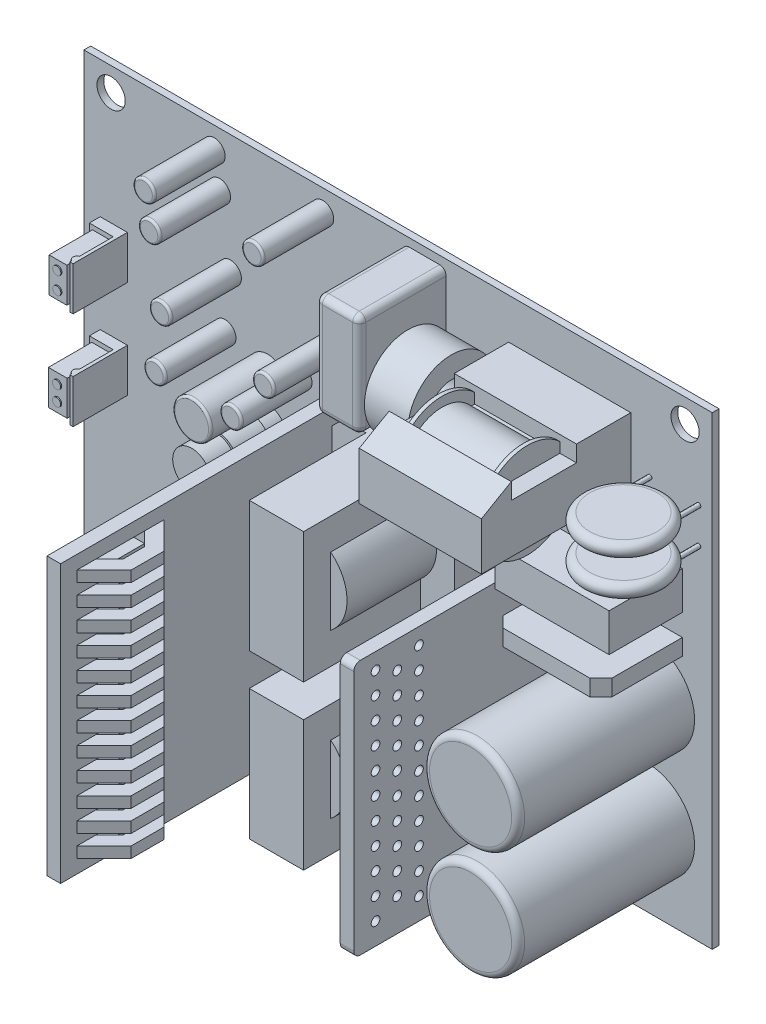
SolidWorks part; units mm, degrees
material "PW50:34:C1:0:1:2:Re:16:"
ref_plane "Front" through (0, 0, 0) normal (0, 0, 1) x (1, 0, 0)
ref_plane "Top" through (0, 0, 0) normal (0, 1, 0) x (1, 0, 0)
ref_plane "Side" through (0, 0, 0) normal (1, 0, 0) x (0, 0, -1)
sketch "Sketch1" plane through (0, 0, 0) normal (0, 0, 1) x (1, 0, 0)
  line L0 (-73.4695, 40.132) -> (-73.4695, -68.58)
  line L2 (-73.4695, -68.58) -> (73.4695, -68.58)
  line L4 (-73.4695, 40.132) -> (73.4695, 40.132)
  line L5 (73.4695, 40.132) -> (73.4695, -68.58)
  circle A3 centre (67.1195, 34.6075) radius 3.302
  circle A5 centre (-67.1195, 34.6075) radius 3.302
extrude "Base-Extrude" add sketch "Sketch1" along normal blind 1.5875
sketch "Sketch3" plane through (0, 0, 1.5875) normal (0, 0, 1) x (1, 0, 0)
  line L0 (73.4695, 40.132) -> (73.4695, -68.58) construction
  line L1 (-73.4695, -68.58) -> (73.4695, -68.58) construction
  circle A0 centre (58.2295, -49.53) radius 11.1125
  circle A1 centre (58.2295, -24.13) radius 11.1125
  dimension "D1" = 22.225
  dimension "D4" = 25.4
  dimension "D2" = 15.24
  dimension "D3" = 19.05
extrude "Boss-Extrude1" add sketch "Sketch3" along normal blind 41.275
fillet "Fillet1" radius 1.524 2 edges at (69.342, -24.13, 42.8625) (69.342, -49.53, 42.8625)
sketch "Sketch4" plane through (0, 0, 1.5875) normal (0, 0, 1) x (1, 0, 0)
  line L0 (66.4845, -8.89) -> (41.0845, -8.89)
  line L1 (66.4845, -8.89) -> (66.4845, -12.7)
  line L2 (41.0845, -12.7) -> (66.4845, -12.7)
  line L3 (41.0845, -12.7) -> (41.0845, -8.89)
  line L4 (-73.4695, -68.58) -> (73.4695, -68.58) construction
  line L5 (73.4695, 40.132) -> (73.4695, -68.58) construction
  dimension "D1" = 25.4
  dimension "D2" = 3.81
  dimension "D3" = 59.69
  dimension "D4" = 6.985
extrude "Boss-Extrude2" add sketch "Sketch4" along normal blind 19.05
chamfer "Chamfer1" distance 2.54 angle 45 2 edges at (66.4845, -10.795, 20.6375) (41.0845, -10.795, 20.6375)
sketch "Sketch5" plane through (0, 0, 1.5875) normal (0, 0, 1) x (1, 0, 0)
  line L0 (39.8145, 5.08) -> (66.4845, 5.08)
  line L1 (39.8145, 5.08) -> (39.8145, -3.81)
  line L2 (66.4845, -3.81) -> (39.8145, -3.81)
  line L3 (66.4845, -3.81) -> (66.4845, 5.08)
  line L4 (-73.4695, -68.58) -> (73.4695, -68.58) construction
  line L5 (73.4695, 40.132) -> (73.4695, -68.58) construction
  dimension "D1" = 26.67
  dimension "D2" = 8.89
  dimension "D3" = 73.66
  dimension "D4" = 6.985
extrude "Boss-Extrude3" add sketch "Sketch5" along normal blind 17.145
ref_plane "Plane4" through (0, 19.812, 0) normal (0, 1, 0) x (-1, 0, 0)
sketch "Sketch6" plane through (0, 19.812, 0) normal (0, 1, 0) x (-1, 0, 0)
  line L0 (-64.5795, -2.54) -> (-64.5795, 29.21) construction
  line L2 (-70.2945, 1.5875) -> (-70.2945, 6.7362)
  line L3 (-58.8645, 1.5875) -> (-58.8645, 6.7362)
  line L6 (73.4695, 1.5875) -> (-73.4695, 1.5875) construction
  arc A0 (-58.2116, 8.7074) -> (-70.9474, 8.7074) centre (-64.5795, 13.4459) ccw
  arc A1 (-58.2116, 8.7074) -> (-58.8645, 6.7362) centre (-55.5625, 6.7362) ccw
  arc A2 (-70.9474, 8.7074) -> (-70.2945, 6.7362) centre (-73.5965, 6.7362) cw
  point P13 (-58.8645, 7.9375)
  dimension "D4" = 3.302
  dimension "D5" = 5.715
  dimension "D6" = 8.89
  dimension "D3" = 7.9375
  dimension "D1" = 5.1487
  dimension "D2" = 11.8584
sketch "Sketch7" plane through (0, 0, 1.5875) normal (0, 0, 1) x (1, 0, 0)
  circle A0 centre (70.2945, 19.812) radius 0.508
  dimension "D1" = 1.016
sweep "Boss-Sweep1" add profiles "Sketch7" path "Sketch6"
ref_plane "Plane5" through (0, 0, 13.4493) normal (0, 0, 1) x (1, 0, 0)
sketch "Sketch8" plane through (0, 0, 13.4493) normal (0, 0, 1) x (1, 0, 0)
  line L0 (73.4695, 40.132) -> (73.4695, -68.58) construction
  line L1 (-73.4695, 40.132) -> (73.4695, 40.132) construction
  line L2 (72.4493, 21.463) -> (64.5795, 21.463)
  line L3 (64.5795, 19.812) -> (64.5795, 13.7195) construction
  line L4 (64.5795, 21.463) -> (64.5795, 18.161)
  line L5 (72.4493, 18.161) -> (64.5795, 18.161)
  arc A0 (72.4493, 18.161) -> (72.4493, 21.463) centre (72.4493, 19.812) ccw
  dimension "D1" = 3.302
  dimension "D2" = 20.32
  dimension "D3" = 1.0202
  dimension "D4" = 8.89
revolve "Boss-Revolve1" add sketch "Sketch8" angle 360 about L3
pattern_linear "LPattern1" count 2 spacing 8.255 along (0, -1, 0) of "Boss-Revolve1", "Boss-Sweep1"
sketch "Sketch9" plane through (0, 0, 1.5875) normal (0, 0, 1) x (1, 0, 0)
  line L0 (25.8445, 30.607) -> (54.4195, 30.607)
  line L1 (25.8445, 30.607) -> (25.8445, 11.557)
  line L2 (54.4195, 11.557) -> (25.8445, 11.557)
  line L3 (54.4195, 11.557) -> (54.4195, 30.607)
  line L4 (-73.4695, 40.132) -> (73.4695, 40.132) construction
  line L5 (73.4695, 40.132) -> (73.4695, -68.58) construction
  dimension "D1" = 28.575
  dimension "D2" = 19.05
  dimension "D3" = 9.525
  dimension "D4" = 19.05
extrude "Boss-Extrude4" add sketch "Sketch9" along normal blind 34.925
sketch "Sketch10" plane through (54.4195, 0, 0) normal (1, 0, 0) x (0, 0, -1)
  line L0 (-29.5275, 30.607) -> (-42.1593, 23.314)
  line L1 (-14.2875, 40.132) -> (-14.2875, -68.58)
  line L2 (-14.2875, 40.132) -> (-14.2875, 26.797)
  line L3 (-29.5275, 40.132) -> (-29.5275, -68.58)
  line L4 (-29.5275, 30.607) -> (-29.5275, 26.797)
  line L5 (-36.5125, 15.367) -> (-1.5875, 15.367)
  line L6 (-42.1593, 15.367) -> (-14.2875, 15.367)
  line L7 (-36.5125, 26.797) -> (-1.5875, 26.797)
  line L8 (-29.5275, 26.797) -> (-14.2875, 26.797)
  line L9 (-36.5125, 30.607) -> (-1.5875, 30.607) construction
  line L10 (-14.2875, 7.4511) -> (-47.8412, 7.4511)
  line L11 (-47.8412, 7.4511) -> (-47.8412, 40.132)
  line L12 (-47.8412, 40.132) -> (-14.2875, 40.132)
  line L13 (-14.2875, 15.367) -> (-14.2875, 7.4511)
  line L14 (-42.1593, 23.314) -> (-42.1593, 15.367)
  dimension "D5" = 27.8718
  dimension "D6" = 33.5537
  dimension "D7" = 32.6809
  dimension "D8" = 30
  dimension "D1" = 12.7
  dimension "D2" = 27.94
  dimension "D3" = 3.81
  dimension "D4" = 3.81
extrude "Cut-Extrude1" cut sketch "Sketch10" against normal through all
ref_plane "Plane6" through (54.4195, 0, 0) normal (-1, 0, 0) x (0, 0, 1)
ref_plane "Plane7" through (40.132, 0, 0) normal (-1, 0, 0) x (0, 0, 1)
sketch "Sketch11" plane through (40.132, 0, 0) normal (-1, 0, 0) x (0, 0, 1)
  line L0 (14.2875, 15.367) -> (14.2875, 26.797) construction
  line L1 (14.2875, 21.082) -> (29.5275, 21.082) construction
  line L3 (29.5275, 30.607) -> (29.5275, 26.797) construction
  circle A0 centre (21.9075, 21.082) radius 8.89
  dimension "D1" = 17.78
extrude "Boss-Extrude5" add sketch "Sketch11" along normal mid plane 19.05
sketch "Sketch12" plane through (49.657, 0, 0) normal (1, 0, 0) x (0, 0, -1)
  circle A0 centre (-21.9075, 21.082) radius 11.1125
  dimension "D1" = 22.225
extrude "Boss-Extrude6" add sketch "Sketch12" along normal blind 0.889
sketch "Sketch13" plane through (30.607, 0, 0) normal (-1, 0, 0) x (0, 0, 1)
  circle A0 centre (21.9075, 21.082) radius 11.1125
  arc A1 (29.5275, 29.1705) -> (14.2875, 29.1705) centre (21.9075, 21.082) ccw construction
extrude "Boss-Extrude7" add sketch "Sketch13" along normal blind 0.889
ref_plane "Plane8" through (17.272, 0, 0) normal (-1, 0, 0) x (0, 0, 1)
sketch "Sketch14" plane through (17.272, 0, 0) normal (-1, 0, 0) x (0, 0, 1)
  line L0 (21.9075, 21.082) -> (15.647, 21.082) construction
  line L1 (1.5875, 40.132) -> (1.5875, -68.58) construction
  circle A0 centre (11.4935, 21.082) radius 10.16
  circle A1 centre (11.4935, 21.082) radius 5.08
  dimension "D1" = 20.32
  dimension "D2" = 10.16
  dimension "D3" = 9.906
extrude "Boss-Extrude8" add sketch "Sketch14" along normal mid plane 10.16
sketch "Sketch15" plane through (0, 0, 1.5875) normal (0, 0, 1) x (1, 0, 0)
  line L0 (2.6035, 14.097) -> (9.7155, 14.097)
  line L1 (1.0795, 15.621) -> (1.0795, 36.703)
  line L2 (9.7155, 38.227) -> (2.6035, 38.227)
  line L3 (11.2395, 36.703) -> (11.2395, 15.621)
  line L4 (73.4695, 40.132) -> (73.4695, -68.58) construction
  line L5 (-73.4695, 40.132) -> (73.4695, 40.132) construction
  arc A0 (1.0795, 15.621) -> (2.6035, 14.097) centre (2.6035, 15.621) ccw
  arc A1 (11.2395, 15.621) -> (9.7155, 14.097) centre (9.7155, 15.621) cw
  arc A2 (11.2395, 36.703) -> (9.7155, 38.227) centre (9.7155, 36.703) ccw
  arc A3 (2.6035, 38.227) -> (1.0795, 36.703) centre (2.6035, 36.703) ccw
  dimension "D5" = 1.524
  dimension "D1" = 62.23
  dimension "D2" = 10.16
  dimension "D3" = 1.905
  dimension "D4" = 24.13
extrude "Boss-Extrude9" add sketch "Sketch15" along normal blind 20.32
fillet "Fillet2" radius 1.524 8 edges at (10.7931, 14.5434, 21.9075) (11.2395, 26.162, 21.9075) (1.0795, 26.162, 21.9075) (1.5259, 14.5434, 21.9075) (6.1595, 14.097, 21.9075) (10.7931, 37.7806, 21.9075) (6.1595, 38.227, 21.9075) (1.5259, 37.7806, 21.9075)
sketch "Sketch16" plane through (0, 0, 1.5875) normal (0, 0, 1) x (1, 0, 0)
  line L0 (33.4645, -5.715) -> (36.6395, -5.715)
  line L1 (33.4645, -5.715) -> (33.4645, -65.405)
  line L2 (36.6395, -65.405) -> (33.4645, -65.405)
  line L3 (36.6395, -65.405) -> (36.6395, -5.715)
  line L4 (73.4695, 40.132) -> (73.4695, -68.58) construction
  line L5 (-73.4695, -68.58) -> (73.4695, -68.58) construction
  dimension "D1" = 36.83
  dimension "D2" = 3.175
  dimension "D3" = 3.175
  dimension "D4" = 59.69
extrude "Boss-Extrude10" add sketch "Sketch16" along normal blind 46.99
fillet "Fillet3" radius 1.524 2 edges at (35.052, -65.405, 48.5775) (35.052, -5.715, 48.5775)
sketch "Sketch17" plane through (36.6395, 0, 0) normal (1, 0, 0) x (0, 0, -1)
  line L0 (-48.5775, -63.881) -> (-48.5775, -7.239) construction
  line L1 (-47.0535, -65.405) -> (-1.5875, -65.405) construction
  circle A0 centre (-43.4975, -60.325) radius 1.016
  circle A2 centre (-33.3375, -60.325) radius 1.016
  dimension "D1" = 2.032
  dimension "D2" = 5.08
  dimension "D3" = 5.08
  dimension "D4" = 10.16
extrude "Cut-Extrude2" cut sketch "Sketch17" against normal through all
pattern_linear "LPattern2" count 11 spacing 5.08 along (0, 1, 0) of "Cut-Extrude2"
sketch "Sketch18" plane through (36.6395, 0, 0) normal (1, 0, 0) x (0, 0, -1)
  circle A0 centre (-38.4175, -57.785) radius 1.016
  circle A1 centre (-43.4975, -60.325) radius 1.016 construction
  circle A2 centre (-43.4975, -55.245) radius 1.016 construction
  dimension "D1" = 5.08
  dimension "D2" = 2.54
extrude "Cut-Extrude3" cut sketch "Sketch18" against normal through all
pattern_linear "LPattern3" count 10 spacing 5.08 along (0, 1, 0) of "Cut-Extrude3"
sketch "Sketch19" plane through (0, 0, 1.5875) normal (0, 0, 1) x (1, 0, 0)
  line L0 (-3.3655, -33.02) -> (20.1295, -33.02)
  line L1 (-5.9055, -35.56) -> (-5.9055, -60.96)
  line L2 (20.1295, -63.5) -> (-3.3655, -63.5)
  line L3 (22.6695, -60.96) -> (22.6695, -35.56)
  line L4 (73.4695, 40.132) -> (73.4695, -68.58) construction
  line L5 (-73.4695, -68.58) -> (73.4695, -68.58) construction
  line L6 (-3.3655, -33.02) -> (-5.9055, -35.56)
  line L9 (-5.9055, -60.96) -> (-3.3655, -63.5)
  line L11 (20.1295, -63.5) -> (22.6695, -60.96)
  line L13 (22.6695, -35.56) -> (20.1295, -33.02)
  dimension "D1" = 135
  dimension "D2" = 45
  dimension "D3" = 135
  dimension "D4" = 135
  dimension "D5" = 28.575
  dimension "D6" = 30.48
  dimension "D7" = 2.54
  dimension "D8" = 50.8
  dimension "D9" = 5.08
extrude "Boss-Extrude11" add sketch "Sketch19" along normal blind 36.83
sketch "Sketch20" plane through (0, 0, 38.4175) normal (0, 0, 1) x (1, 0, 0)
  line L0 (22.6695, -48.26) -> (-5.9055, -48.26) construction
  line L3 (22.6695, -60.96) -> (22.6695, -35.56) construction
  line L4 (-5.9055, -35.56) -> (-5.9055, -60.96) construction
  line L5 (8.382, -48.26) -> (8.382, -24.765) construction
  line L6 (33.4645, -24.765) -> (36.6395, -24.765) construction
  line L7 (2.032, -29.21) -> (2.032, -40.3289)
  line L9 (14.732, -29.21) -> (14.732, -40.3289)
  line L10 (2.032, -29.21) -> (-4.9437, -29.21)
  line L11 (2.032, -56.1911) -> (2.032, -67.31)
  line L12 (14.732, -56.1911) -> (14.732, -67.31)
  line L13 (14.732, -67.31) -> (21.7077, -67.31)
  line L18 (-4.9437, -29.21) -> (-9.7155, -33.9818)
  line L19 (-9.7155, -33.9818) -> (-9.7155, -62.5382)
  line L20 (-9.7155, -62.5382) -> (-4.9437, -67.31)
  line L21 (-4.9437, -67.31) -> (21.7077, -67.31)
  line L22 (21.7077, -67.31) -> (26.4795, -62.5382)
  line L23 (26.4795, -62.5382) -> (26.4795, -33.9818)
  line L24 (26.4795, -33.9818) -> (21.7077, -29.21)
  line L25 (21.7077, -29.21) -> (-4.9437, -29.21)
  line L26 (-4.9437, -29.21) -> (-9.7155, -33.9818)
  line L27 (-9.7155, -33.9818) -> (-9.7155, -62.5382)
  line L28 (-9.7155, -62.5382) -> (-4.9437, -67.31)
  line L29 (-4.9437, -67.31) -> (2.032, -67.31)
  line L30 (21.7077, -67.31) -> (26.4795, -62.5382)
  line L31 (26.4795, -62.5382) -> (26.4795, -33.9818)
  line L32 (26.4795, -33.9818) -> (21.7077, -29.21)
  line L33 (21.7077, -29.21) -> (14.732, -29.21)
  arc A0 (2.032, -40.3289) -> (2.032, -56.1911) centre (8.382, -48.26) ccw
  arc A1 (14.732, -56.1911) -> (14.732, -40.3289) centre (8.382, -48.26) ccw
  dimension "D2" = 20.32
  dimension "D1" = 12.7
  dimension "D3" = 3.81
extrude "Cut-Extrude4" cut sketch "Sketch20" against normal offset from surface (27.305 mm away) 9.525
sketch "Sketch21" plane through (0, 0, 38.4175) normal (0, 0, 1) x (1, 0, 0)
  line L0 (2.032, -33.02) -> (2.032, -40.3289) construction
  line L1 (2.032, -37.3547) -> (2.032, -59.1653)
  line L2 (14.732, -33.02) -> (14.732, -40.3289) construction
  line L3 (14.732, -37.3547) -> (14.732, -59.1653)
  line L4 (-0.3493, -37.3547) -> (2.032, -37.3547)
  line L5 (-0.3493, -59.1653) -> (2.032, -59.1653)
  line L6 (14.732, -37.3547) -> (17.1132, -37.3547)
  line L7 (14.732, -59.1653) -> (17.1132, -59.1653)
  arc A1 (17.1132, -59.1653) -> (17.1132, -37.3547) centre (8.382, -48.26) ccw
  arc A2 (17.1132, -59.1653) -> (17.1132, -37.3547) centre (8.382, -48.26) ccw
  arc A3 (-0.3493, -37.3547) -> (-0.3493, -59.1653) centre (8.382, -48.26) ccw
  arc A4 (-0.3493, -37.3547) -> (-0.3493, -59.1653) centre (8.382, -48.26) ccw
  dimension "D1" = 3.81
  dimension "D2" = 3.81
extrude "Cut-Extrude5" cut sketch "Sketch21" against normal blind 6.35
pattern_linear "LPattern4" count 2 spacing 38.1 along (0, 1, 0) of "Cut-Extrude5", "Cut-Extrude4", "Boss-Extrude11"
sketch "Sketch22" plane through (0, 0, 1.5875) normal (0, 0, 1) x (1, 0, 0)
  line L0 (-16.0655, -0.635) -> (-12.8905, -0.635)
  line L1 (-16.0655, -0.635) -> (-16.0655, -65.405)
  line L2 (-12.8905, -65.405) -> (-16.0655, -65.405)
  line L3 (-12.8905, -65.405) -> (-12.8905, -0.635)
  line L4 (-73.4695, -68.58) -> (73.4695, -68.58) construction
  line L5 (73.4695, 40.132) -> (73.4695, -68.58) construction
  dimension "D1" = 3.175
  dimension "D2" = 3.175
  dimension "D3" = 64.77
  dimension "D4" = 86.36
extrude "Boss-Extrude12" add sketch "Sketch22" along normal blind 66.04
sketch "Sketch23" plane through (0, -0.635, 0) normal (0, 1, 0) x (-1, 0, 0)
  line L0 (12.8905, 63.8175) -> (6.5405, 57.4675)
  line L1 (12.8905, 67.6275) -> (12.8905, 1.5875) construction
  line L2 (6.5405, 57.4675) -> (6.5405, 49.8475)
  line L3 (6.5405, 49.8475) -> (12.8905, 43.4975)
  line L4 (12.8905, 47.9876) -> (9.7155, 51.1626)
  line L5 (9.7155, 51.1626) -> (9.7155, 56.1524)
  line L6 (9.7155, 56.1524) -> (12.8905, 59.3274)
  line L7 (12.8905, 59.3274) -> (12.8905, 63.8175)
  line L8 (12.8905, 47.9876) -> (12.8905, 43.4975)
  line L9 (16.0655, 67.6275) -> (12.8905, 67.6275) construction
  dimension "D1" = 3.175
  dimension "D2" = 3.175
  dimension "D3" = 135
  dimension "D4" = 135
  dimension "D5" = 3.175
  dimension "D6" = 3.175
  dimension "D7" = 3.81
  dimension "D8" = 20.32
extrude "Boss-Extrude13" add sketch "Sketch23" against normal up to surface (64.77 mm away) up to face at (-14.478, -65.405, 34.6075)
sketch "Sketch24" plane through (0, 0, 67.6275) normal (0, 0, 1) x (1, 0, 0)
  line L2 (-16.1074, -32.385) -> (-48.09, -32.385) construction
  line L4 (-12.8905, -19.05) -> (-12.8905, -16.51)
  line L5 (-12.8905, -24.13) -> (-12.8905, -21.59)
  line L6 (-12.8905, -8.89) -> (-6.2865, -8.89)
  line L8 (-12.8905, -29.21) -> (-12.8905, -26.67)
  line L9 (-6.2865, -69.85) -> (-6.2865, -62.23)
  line L10 (-12.8905, -69.85) -> (-12.8905, -62.23)
  line L11 (-12.8905, -34.29) -> (-12.8905, -31.75)
  line L12 (-12.8905, -6.35) -> (-6.2865, -6.35)
  line L13 (-12.8905, -11.43) -> (-6.2865, -11.43)
  line L14 (-12.8905, -13.97) -> (-6.2865, -13.97)
  line L15 (-12.8905, -16.51) -> (-6.2865, -16.51)
  line L16 (-12.8905, -19.05) -> (-6.2865, -19.05)
  line L17 (-6.2865, -8.89) -> (-6.2865, -6.35)
  line L18 (-12.8905, -8.89) -> (-12.8905, -6.35)
  line L19 (-12.8905, -13.97) -> (-12.8905, -11.43)
  line L20 (-6.2865, -13.97) -> (-6.2865, -11.43)
  line L21 (-12.8905, -21.59) -> (-6.2865, -21.59)
  line L22 (-12.8905, -24.13) -> (-6.2865, -24.13)
  line L23 (-12.8905, -26.67) -> (-6.2865, -26.67)
  line L25 (-12.8905, -29.21) -> (-6.2865, -29.21)
  line L26 (-12.8905, -31.75) -> (-6.2865, -31.75)
  line L27 (-12.8905, -34.29) -> (-6.2865, -34.29)
  line L29 (-12.8905, -36.83) -> (-6.2865, -36.83)
  line L30 (-12.8905, -39.37) -> (-6.2865, -39.37)
  line L31 (-12.8905, -41.91) -> (-6.2865, -41.91)
  line L33 (-12.8905, -44.45) -> (-6.2865, -44.45)
  line L34 (-12.8905, -46.99) -> (-6.2865, -46.99)
  line L36 (-12.8905, -49.53) -> (-6.2865, -49.53)
  line L38 (-12.8905, -52.07) -> (-6.2865, -52.07)
  line L39 (-12.8905, -54.61) -> (-6.2865, -54.61)
  line L40 (-12.8905, -57.15) -> (-6.2865, -57.15)
  line L41 (-12.8905, -39.37) -> (-12.8905, -36.83)
  line L42 (-12.8905, -44.45) -> (-12.8905, -41.91)
  line L43 (-12.8905, -49.53) -> (-12.8905, -46.99)
  line L44 (-12.8905, -54.61) -> (-12.8905, -52.07)
  line L45 (-6.2865, -54.61) -> (-6.2865, -52.07)
  line L46 (-6.2865, -49.53) -> (-6.2865, -46.99)
  line L47 (-6.2865, -44.45) -> (-6.2865, -41.91)
  line L48 (-6.2865, -39.37) -> (-6.2865, -36.83)
  line L49 (-6.2865, -34.29) -> (-6.2865, -31.75)
  line L50 (-6.2865, -29.21) -> (-6.2865, -26.67)
  line L51 (-6.2865, -24.13) -> (-6.2865, -21.59)
  line L52 (-6.2865, -19.05) -> (-6.2865, -16.51)
  line L53 (-6.2865, -59.69) -> (-12.8905, -59.69)
  line L55 (-6.2865, -62.23) -> (-12.8905, -62.23)
  line L57 (-6.2865, -69.85) -> (-12.8905, -69.85)
  line L61 (-6.2865, -59.69) -> (-6.2865, -57.15)
  line L62 (-12.8905, -59.69) -> (-12.8905, -57.15)
  line L63 (-12.8905, -65.405) -> (-12.8905, -0.635) construction
  line L64 (-12.8905, -65.405) -> (-6.5405, -65.405) construction
  line L65 (-12.8905, -3.81) -> (-6.2865, -3.81)
  line L67 (-12.8905, -3.81) -> (-12.8905, -0.381)
  line L68 (-12.8905, -0.381) -> (-6.5405, -0.381)
  line L69 (-12.8905, -0.381) -> (-6.2865, -0.381)
  line L70 (-6.2865, -3.81) -> (-6.2865, -0.381)
  line L71 (-16.0655, -0.635) -> (-12.8905, -0.635) construction
  dimension "D2" = 2.54
  dimension "D4" = 2.54
  dimension "D5" = 2.54
  dimension "D6" = 2.54
  dimension "D7" = 2.54
  dimension "D8" = 2.54
  dimension "D9" = 2.54
  dimension "D10" = 2.54
  dimension "D11" = 2.54
  dimension "D12" = 2.54
  dimension "D13" = 2.54
  dimension "D14" = 2.54
  dimension "D15" = 2.54
  dimension "D16" = 2.54
  dimension "D17" = 2.54
  dimension "D18" = 2.54
  dimension "D1" = 2.54
  dimension "D3" = 2.54
  dimension "D19" = 2.54
  dimension "D20" = 2.54
  dimension "D21" = 63.5
  dimension "D22" = 3.175
  dimension "D23" = 2.54
  dimension "D24" = 2.54
  dimension "D25" = 6.604
  dimension "D26" = 2.54
  dimension "D27" = 0.254
  dimension "D28" = 3.175
extrude "Cut-Extrude6" cut sketch "Sketch24" against normal blind 25.4
sketch "Sketch25" plane through (-16.0655, 0, 0) normal (-1, 0, 0) x (0, 0, 1)
  line L0 (56.1524, -62.23) -> (51.1626, -62.23) construction
  line L1 (56.1524, -59.69) -> (51.1626, -59.69) construction
  line L2 (51.1626, -57.15) -> (56.1524, -57.15) construction
  line L3 (51.1626, -54.61) -> (56.1524, -54.61) construction
  line L4 (51.1626, -52.07) -> (56.1524, -52.07) construction
  line L5 (51.1626, -49.53) -> (56.1524, -49.53) construction
  line L6 (51.1626, -46.99) -> (56.1524, -46.99) construction
  line L7 (51.1626, -44.45) -> (56.1524, -44.45) construction
  line L8 (51.1626, -41.91) -> (56.1524, -41.91) construction
  line L9 (51.1626, -39.37) -> (56.1524, -39.37) construction
  line L10 (51.1626, -36.83) -> (56.1524, -36.83) construction
  line L11 (51.1626, -34.29) -> (56.1524, -34.29) construction
  line L12 (51.1626, -31.75) -> (56.1524, -31.75) construction
  line L13 (51.1626, -29.21) -> (56.1524, -29.21) construction
  line L14 (51.1626, -26.67) -> (56.1524, -26.67) construction
  line L15 (51.1626, -24.13) -> (56.1524, -24.13) construction
  line L16 (51.1626, -21.59) -> (56.1524, -21.59) construction
  line L17 (51.1626, -19.05) -> (56.1524, -19.05) construction
  line L18 (51.1626, -16.51) -> (56.1524, -16.51) construction
  line L19 (51.1626, -13.97) -> (56.1524, -13.97) construction
  line L20 (51.1626, -11.43) -> (56.1524, -11.43) construction
  line L21 (51.1626, -8.89) -> (56.1524, -8.89) construction
  line L22 (51.1626, -3.81) -> (56.1524, -3.81) construction
  line L23 (51.1626, -6.35) -> (56.1524, -6.35) construction
  line L24 (59.3274, -62.23) -> (47.9876, -62.23)
  line L25 (59.3274, -59.69) -> (47.9876, -59.69)
  line L26 (47.9876, -57.15) -> (59.3274, -57.15)
  line L27 (47.9876, -54.61) -> (59.3274, -54.61)
  line L28 (47.9876, -52.07) -> (59.3274, -52.07)
  line L29 (47.9876, -49.53) -> (59.3274, -49.53)
  line L30 (47.9876, -46.99) -> (59.3274, -46.99)
  line L31 (47.9876, -44.45) -> (59.3274, -44.45)
  line L32 (47.9876, -41.91) -> (59.3274, -41.91)
  line L33 (47.9876, -39.37) -> (59.3274, -39.37)
  line L34 (47.9876, -36.83) -> (59.3274, -36.83)
  line L35 (47.9876, -34.29) -> (59.3274, -34.29)
  line L36 (47.9876, -31.75) -> (59.3274, -31.75)
  line L37 (47.9876, -29.21) -> (59.3274, -29.21)
  line L38 (47.9876, -26.67) -> (59.3274, -26.67)
  line L39 (47.9876, -24.13) -> (59.3274, -24.13)
  line L40 (47.9876, -21.59) -> (59.3274, -21.59)
  line L41 (47.9876, -19.05) -> (59.3274, -19.05)
  line L42 (47.9876, -16.51) -> (59.3274, -16.51)
  line L43 (47.9876, -13.97) -> (59.3274, -13.97)
  line L44 (47.9876, -11.43) -> (59.3274, -11.43)
  line L45 (47.9876, -8.89) -> (59.3274, -8.89)
  line L46 (47.9876, -3.81) -> (59.3274, -3.81)
  line L47 (47.9876, -6.35) -> (59.3274, -6.35)
  line L48 (47.9876, -6.35) -> (47.9876, -3.81) construction
  line L49 (47.9876, -62.23) -> (47.9876, -59.69)
  line L50 (59.3274, -6.35) -> (59.3274, -3.81) construction
  line L51 (59.3274, -62.23) -> (59.3274, -59.69)
  line L52 (43.4975, -62.23) -> (47.9876, -62.23) construction
  line L53 (59.3274, -62.23) -> (63.8175, -62.23) construction
  line L54 (59.3274, -57.15) -> (59.3274, -54.61)
  line L55 (59.3274, -46.99) -> (59.3274, -44.45)
  line L56 (59.3274, -41.91) -> (59.3274, -39.37)
  line L57 (59.3274, -36.83) -> (59.3274, -34.29)
  line L58 (59.3274, -31.75) -> (59.3274, -29.21)
  line L59 (59.3274, -26.67) -> (59.3274, -24.13)
  line L60 (59.3274, -21.59) -> (59.3274, -19.05)
  line L61 (59.3274, -16.51) -> (59.3274, -13.97)
  line L62 (59.3274, -11.43) -> (59.3274, -8.89)
  line L63 (59.3274, -6.35) -> (59.3274, -3.81)
  line L64 (47.9876, -6.35) -> (47.9876, -3.81)
  line L65 (47.9876, -11.43) -> (47.9876, -8.89)
  line L66 (47.9876, -16.51) -> (47.9876, -13.97)
  line L67 (47.9876, -21.59) -> (47.9876, -19.05)
  line L68 (47.9876, -26.67) -> (47.9876, -24.13)
  line L69 (47.9876, -31.75) -> (47.9876, -29.21)
  line L70 (47.9876, -36.83) -> (47.9876, -34.29)
  line L71 (47.9876, -41.91) -> (47.9876, -39.37)
  line L72 (47.9876, -46.99) -> (47.9876, -44.45)
  line L73 (47.9876, -52.07) -> (47.9876, -49.53)
  line L74 (47.9876, -57.15) -> (47.9876, -54.61)
  line L75 (59.3274, -52.07) -> (59.3274, -49.53)
extrude "Cut-Extrude7" cut sketch "Sketch25" against normal up to next
sketch "Sketch26" plane through (-16.0655, 0, 0) normal (-1, 0, 0) x (0, 0, 1)
  line L0 (9.2075, -10.795) -> (29.5275, -10.795)
  line L1 (1.5875, -12.065) -> (1.5875, -14.605)
  line L2 (29.5275, -26.035) -> (9.2075, -26.035)
  line L3 (29.5275, -26.035) -> (29.5275, -10.795)
  line L4 (1.5875, -24.765) -> (9.2075, -24.765)
  line L5 (1.5875, -14.605) -> (9.2075, -14.605)
  line L6 (1.5875, -12.065) -> (9.2075, -12.065)
  line L7 (9.2075, -17.145) -> (1.5875, -17.145)
  line L8 (9.2075, -17.145) -> (9.2075, -14.605)
  line L9 (1.5875, -19.685) -> (9.2075, -19.685)
  line L10 (1.5875, -22.225) -> (1.5875, -24.765)
  line L11 (9.2075, -22.225) -> (1.5875, -22.225)
  line L12 (9.2075, -26.035) -> (9.2075, -24.765)
  line L13 (1.5875, -17.145) -> (1.5875, -19.685)
  line L14 (9.2075, -12.065) -> (9.2075, -10.795)
  line L15 (9.2075, -22.225) -> (9.2075, -19.685)
  line L16 (1.5875, 40.132) -> (1.5875, -68.58) construction
  line L17 (67.6275, -0.635) -> (1.5875, -0.635) construction
  line L18 (67.6275, -33.02) -> (105.41, -33.02) construction
  line L19 (67.6275, -0.635) -> (67.6275, -65.405) construction
  line L20 (9.2075, -43.815) -> (9.2075, -46.355)
  line L21 (9.2075, -53.975) -> (9.2075, -55.245)
  line L22 (1.5875, -48.895) -> (1.5875, -46.355)
  line L23 (9.2075, -40.005) -> (9.2075, -41.275)
  line L24 (9.2075, -43.815) -> (1.5875, -43.815)
  line L25 (1.5875, -43.815) -> (1.5875, -41.275)
  line L26 (1.5875, -46.355) -> (9.2075, -46.355)
  line L27 (9.2075, -48.895) -> (9.2075, -51.435)
  line L28 (9.2075, -48.895) -> (1.5875, -48.895)
  line L29 (1.5875, -53.975) -> (9.2075, -53.975)
  line L30 (1.5875, -51.435) -> (9.2075, -51.435)
  line L31 (1.5875, -41.275) -> (9.2075, -41.275)
  line L32 (29.5275, -40.005) -> (29.5275, -55.245)
  line L33 (29.5275, -40.005) -> (9.2075, -40.005)
  line L34 (1.5875, -53.975) -> (1.5875, -51.435)
  line L35 (9.2075, -55.245) -> (29.5275, -55.245)
  dimension "D1" = 15.24
  dimension "D2" = 2.54
  dimension "D3" = 2.54
  dimension "D4" = 2.54
  dimension "D5" = 2.54
  dimension "D6" = 2.54
  dimension "D7" = 1.27
  dimension "D8" = 27.94
  dimension "D9" = 7.62
  dimension "D10" = 10.16
extrude "Boss-Extrude14" add sketch "Sketch26" along normal blind 1.524
sketch "Sketch27" plane through (-17.5895, 0, 0) normal (-1, 0, 0) x (0, 0, 1)
  line L0 (9.2075, -10.795) -> (29.5275, -10.795) construction
  line L1 (9.4615, -22.225) -> (9.4615, -19.685)
  line L2 (9.4615, -55.245) -> (9.4615, -40.005)
  line L3 (24.4475, -26.035) -> (24.4475, -10.795)
  line L4 (24.4475, -55.245) -> (24.4475, -40.005)
  line L5 (9.4615, -10.795) -> (24.4475, -10.795)
  line L6 (29.5275, -26.035) -> (9.2075, -26.035) construction
  line L7 (24.4475, -26.035) -> (9.4615, -26.035)
  line L8 (29.5275, -40.005) -> (9.2075, -40.005) construction
  line L9 (24.4475, -40.005) -> (9.4615, -40.005)
  line L10 (9.2075, -55.245) -> (29.5275, -55.245) construction
  line L11 (9.4615, -55.245) -> (24.4475, -55.245)
  line L12 (24.4475, -26.035) -> (24.4475, -10.795)
  line L13 (9.4615, -26.035) -> (9.4615, -10.795)
  dimension "D1" = 0.254
  dimension "D2" = 5.08
extrude "Boss-Extrude15" add sketch "Sketch27" along normal blind 2.54
ref_plane "Plane9" through (0, 0, 13.462) normal (0, 0, 1) x (1, 0, 0)
sketch "Sketch28" plane through (0, 0, 13.462) normal (0, 0, 1) x (1, 0, 0)
  line L0 (-12.8905, -33.02) -> (-50.8, -33.02) construction
  line L1 (-12.8905, -65.405) -> (-12.8905, -0.635) construction
  line L2 (-33.3712, -39.878) -> (-26.2255, -39.878)
  line L3 (-36.6732, -43.18) -> (-36.6732, -43.434)
  line L4 (-26.2255, -46.736) -> (-33.3712, -46.736)
  line L5 (-22.9235, -43.434) -> (-22.9235, -43.18)
  line L6 (-16.0655, -0.635) -> (-16.0655, -65.405) construction
  arc A0 (-22.9235, -43.434) -> (-26.2255, -46.736) centre (-26.2255, -43.434) cw
  arc A1 (-33.3712, -46.736) -> (-36.6732, -43.434) centre (-33.3712, -43.434) cw
  arc A2 (-22.9235, -43.18) -> (-26.2255, -39.878) centre (-26.2255, -43.18) ccw
  arc A3 (-36.6732, -43.18) -> (-33.3712, -39.878) centre (-33.3712, -43.18) cw
  dimension "D1" = 3.302
  dimension "D3" = 3.302
  dimension "D4" = 7.1457
  dimension "D5" = 10.16
  dimension "D2" = 6.858
  dimension "D6" = 13.716
revolve "Boss-Revolve2" add sketch "Sketch28" angle 360 about L0
sketch "Sketch29" plane through (0, 0, 1.5875) normal (0, 0, 1) x (1, 0, 0)
  line L0 (-16.0655, -0.635) -> (-12.8905, -0.635) construction
  line L1 (73.4695, 40.132) -> (73.4695, -68.58) construction
  line L2 (-73.4695, 40.132) -> (-73.4695, -68.58) construction
  line L3 (-73.4695, 40.132) -> (73.4695, 40.132) construction
  circle A0 centre (-42.9895, 35.052) radius 2.54
  circle A1 centre (-41.7195, 27.432) radius 2.54
  circle A2 centre (-17.5895, 35.052) radius 2.54
  circle A3 centre (-15.0495, 9.652) radius 2.54
  circle A4 centre (-39.1795, 12.192) radius 2.54
  circle A5 centre (-40.4495, -0.508) radius 2.54
  circle A6 centre (-22.6695, -0.635) radius 2.54
  dimension "D1" = 5.08
  dimension "D3" = 30.48
  dimension "D4" = 31.75
  dimension "D5" = 34.29
  dimension "D6" = 33.02
  dimension "D7" = 50.8
  dimension "D2" = 91.059
  dimension "D8" = 58.42
  dimension "D9" = 5.08
  dimension "D10" = 12.7
  dimension "D11" = 27.94
  dimension "D12" = 30.48
  dimension "D13" = 40.64
extrude "Boss-Extrude16" add sketch "Sketch29" along normal blind 16.51
fillet "Fillet4" radius 0.508 7 edges at (-20.1295, -0.635, 18.0975) (-37.9095, -0.508, 18.0975) (-36.6395, 12.192, 18.0975) (-15.0495, 35.052, 18.0975) (-39.1795, 27.432, 18.0975) (-40.4495, 35.052, 18.0975) (-12.5095, 9.652, 18.0975)
sketch "Sketch30" plane through (0, 0, 1.5875) normal (0, 0, 1) x (1, 0, 0)
  line L0 (33.4645, -14.605) -> (36.6395, -14.605) construction
  line L1 (-73.4695, 40.132) -> (73.4695, 40.132) construction
  line L2 (-73.4695, 40.132) -> (-73.4695, -68.58) construction
  circle A0 centre (-30.48, -4.445) radius 4.445
  circle A1 centre (-30.48, -14.605) radius 4.445
  dimension "D1" = 8.89
  dimension "D2" = 10.16
  dimension "D3" = 44.577
  dimension "D4" = 42.9895
extrude "Boss-Extrude17" add sketch "Sketch30" along normal blind 17.78
fillet "Fillet5" radius 0.508 1 edges at (-26.035, -4.445, 19.3675)
sketch "Sketch31" plane through (0, 0, 13.462) normal (0, 0, 1) x (1, 0, 0)
  circle A1 centre (-30.48, -14.605) radius 4.953
  circle A2 centre (-30.48, -14.605) radius 4.953
  dimension "D1" = 0.508
extrude "Boss-Extrude22" add sketch "Sketch31" against normal blind 7.62
sketch "Sketch32" plane through (0, 0, 1.5875) normal (0, 0, 1) x (1, 0, 0)
  line L0 (33.4645, -57.785) -> (36.6395, -57.785) construction
  line L1 (33.4645, -45.085) -> (36.6395, -45.085) construction
  line L2 (-73.4695, -68.58) -> (73.4695, -68.58) construction
  line L3 (-73.4695, 40.132) -> (-73.4695, -68.58) construction
  circle A0 centre (-31.5595, -57.785) radius 6.35
  circle A1 centre (-50.6095, -45.085) radius 6.35
  dimension "D1" = 12.7
  dimension "D2" = 10.795
  dimension "D3" = 41.91
  dimension "D4" = 22.86
  dimension "D5" = 23.495
extrude "Boss-Extrude23" add sketch "Sketch32" along normal blind 20.32
fillet "Fillet6" radius 0.762 2 edges at (-25.2095, -57.785, 21.9075) (-44.2595, -45.085, 21.9075)
sketch "Sketch33" plane through (0, 0, 1.5875) normal (0, 0, 1) x (1, 0, 0)
  line L0 (-69.6595, -14.605) -> (-63.3095, -14.605)
  line L1 (-69.6595, -14.605) -> (-69.6595, -24.765)
  line L2 (-63.3095, -24.765) -> (-69.6595, -24.765)
  line L3 (-63.3095, -24.765) -> (-63.3095, -14.605)
  line L7 (-73.4695, 40.132) -> (-73.4695, -68.58) construction
  line L8 (-73.4695, 40.132) -> (73.4695, 40.132) construction
  dimension "D1" = 10.16
  dimension "D2" = 6.35
  dimension "D3" = 3.81
  dimension "D4" = 54.737
extrude "Boss-Extrude24" add sketch "Sketch33" along normal blind 12.7
sketch "Sketch34" plane through (0, -14.605, 0) normal (0, 1, 0) x (-1, 0, 0)
  line L0 (69.6595, 14.2875) -> (63.3095, 14.2875) construction
  line L1 (73.4695, 4.1275) -> (-73.4695, 4.1275)
  line L2 (70.4215, 4.1275) -> (64.0715, 4.1275)
  line L3 (64.0715, 14.2875) -> (64.0715, 1.5875)
  line L4 (64.0715, 15.0495) -> (64.0715, 13.8354)
  line L5 (64.0715, 12.0443) -> (64.0715, 4.1275)
  line L6 (70.4215, 15.0495) -> (63.3095, 15.0495)
  line L7 (70.4215, 15.0495) -> (70.4215, 1.5875)
  line L8 (70.4215, 15.0495) -> (64.0715, 15.0495)
  line L9 (70.4215, 15.0495) -> (70.4215, 4.1275)
  arc A0 (64.0715, 12.0443) -> (64.0715, 13.8354) centre (63.7415, 12.9399) ccw
  dimension "D4" = 0.9544
  dimension "D5" = 1.3476
  dimension "D6" = 0.33
  dimension "D1" = 2.54
  dimension "D2" = 0.762
  dimension "D3" = 0.762
extrude "Cut-Extrude8" cut sketch "Sketch34" against normal blind 12.7
sketch "Sketch35" plane through (0, 0, 4.1275) normal (0, 0, 1) x (1, 0, 0)
  line L0 (-69.6595, -19.685) -> (-59.0894, -19.685) construction
  line L2 (-69.6595, -14.605) -> (-69.6595, -24.765) construction
  line L3 (-68.1355, -16.891) -> (-66.6115, -16.891)
  line L4 (-68.1355, -16.891) -> (-68.1355, -18.415)
  line L5 (-66.6115, -18.415) -> (-68.1355, -18.415)
  line L6 (-66.6115, -18.415) -> (-66.6115, -16.891)
  line L7 (-68.1355, -22.479) -> (-66.6115, -22.479)
  line L8 (-68.1355, -22.479) -> (-68.1355, -20.955)
  line L9 (-66.6115, -20.955) -> (-68.1355, -20.955)
  line L10 (-66.6115, -20.955) -> (-66.6115, -22.479)
  dimension "D1" = 1.524
  dimension "D2" = 1.524
  dimension "D3" = 5.588
extrude "Boss-Extrude25" add sketch "Sketch35" along normal blind 8.89
sketch "Sketch36" plane through (0, 0, 4.1275) normal (0, 0, 1) x (1, 0, 0)
  line L0 (-64.6724, -15.621) -> (-69.088, -15.621)
  line L1 (-64.6724, -15.621) -> (-64.6724, -23.749)
  line L2 (-69.088, -23.749) -> (-64.6724, -23.749)
  line L3 (-69.088, -23.749) -> (-69.088, -22.479)
  line L4 (-69.088, -16.891) -> (-66.6115, -16.891)
  line L6 (-66.6115, -22.479) -> (-69.088, -22.479)
  line L7 (-66.6115, -22.479) -> (-66.6115, -16.891)
  line L8 (-68.1355, -22.479) -> (-66.6115, -22.479) construction
  line L9 (-68.1355, -16.891) -> (-66.6115, -16.891) construction
  line L10 (-69.088, -16.891) -> (-69.088, -15.621)
  dimension "D1" = 1.27
  dimension "D2" = 1.27
extrude "Boss-Extrude26" add sketch "Sketch36" along normal up to surface (8.89 mm away) up to face at (-67.3735, -17.653, 13.0175)
sketch "Sketch37" plane through (0, 0, 13.0175) normal (0, 0, 1) x (1, 0, 0)
  line L0 (-64.6927, -15.621) -> (-69.088, -15.621)
  line L1 (-64.6927, -15.621) -> (-64.6927, -23.749)
  line L2 (-69.088, -23.749) -> (-64.6927, -23.749)
  line L3 (-69.088, -23.749) -> (-69.088, -15.621)
extrude "Boss-Extrude27" add sketch "Sketch37" along normal blind 1.27
sketch "Sketch38" plane through (0, 0, 14.2875) normal (0, 0, 1) x (1, 0, 0)
  line L0 (-69.088, -19.685) -> (-65.3313, -19.685) construction
  line L1 (-69.088, -23.749) -> (-69.088, -15.621) construction
  circle A0 centre (-66.9276, -17.9163) radius 0.9525
  circle A1 centre (-66.9276, -21.4537) radius 0.9525
  dimension "D1" = 1.905
extrude "Boss-Extrude28" add sketch "Sketch38" along normal blind 0.254
ref_plane "Plane10" through (-66.9276, 0, 0) normal (-1, 0, 0) x (0, 0, 1)
pattern_linear "LPattern8" count 2 spacing 22.86 along (0, 1, 0) of "Boss-Extrude25", "Cut-Extrude8", "Boss-Extrude24"
sketch "Sketch47" plane through (0, 0, 4.1275) normal (0, 0, 1) x (1, 0, 0)
  line L0 (-64.77, 7.239) -> (-68.9243, 7.239)
  line L1 (-64.77, 7.239) -> (-64.77, -0.889)
  line L2 (-68.9243, -0.889) -> (-64.77, -0.889)
  line L3 (-68.9243, -0.889) -> (-68.9243, 0.381)
  line L4 (-68.9243, 5.969) -> (-66.6115, 5.969)
  line L6 (-66.6115, 0.381) -> (-68.9243, 0.381)
  line L7 (-66.6115, 0.381) -> (-66.6115, 5.969)
  line L8 (-68.9243, 5.969) -> (-68.9243, 7.239)
  dimension "D1" = 1.27
  dimension "D2" = 1.27
extrude "Boss-Extrude29" add sketch "Sketch47" along normal up to surface (8.89 mm away) up to face at (-67.3735, 5.207, 13.0175)
sketch "Sketch48" plane through (0, 0, 13.0175) normal (0, 0, 1) x (1, 0, 0)
  line L0 (-64.77, 7.239) -> (-68.9243, 7.239)
  line L1 (-64.77, 7.239) -> (-64.77, -0.889)
  line L2 (-68.9243, -0.889) -> (-64.77, -0.889)
  line L3 (-68.9243, -0.889) -> (-68.9243, 7.239)
extrude "Boss-Extrude30" add sketch "Sketch48" along normal blind 1.27
sketch "Sketch51" plane through (0, 0, 14.2875) normal (0, 0, 1) x (1, 0, 0)
  line L0 (-68.9243, 3.175) -> (-66.1467, 3.175) construction
  line L1 (-68.9243, -0.889) -> (-68.9243, 7.239) construction
  circle A0 centre (-66.8706, 5.2042) radius 0.9525
  circle A1 centre (-66.8706, 1.1458) radius 0.9525
  dimension "D1" = 1.905
extrude "Boss-Extrude31" add sketch "Sketch51" along normal blind 0.254
scale "Scale1" scale about centroid uniform scaling yes scale factor 0.6
